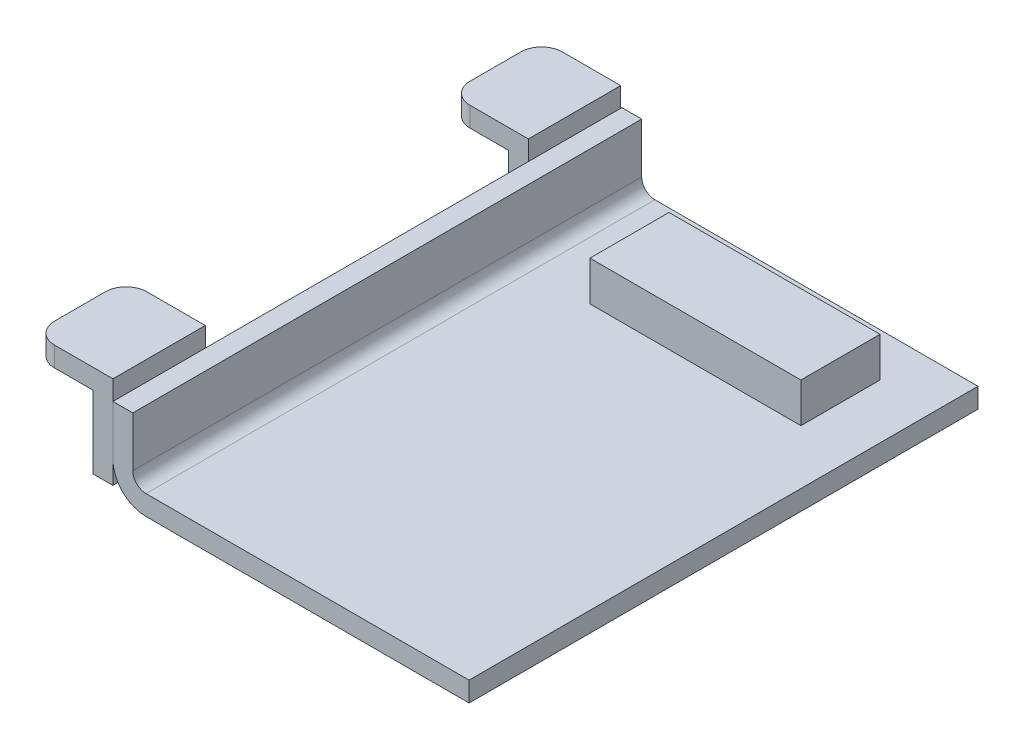
SolidWorks part; units mm, degrees
material "Aluminum Black Anodize"
ref_plane "Front" through (0, 0, 0) normal (0, 0, 1) x (1, 0, 0)
ref_plane "Top" through (0, 0, 0) normal (0, 1, 0) x (1, 0, 0)
ref_plane "Right" through (0, 0, 0) normal (1, 0, 0) x (0, 0, -1)
sketch "Sketch1" plane through (0, 0, 0) normal (0, 0, 1) x (1, 0, 0)
  line L0 (0, 0) -> (0, 20)
  line L1 (0, 20) -> (4.7752, 20)
  line L2 (4.7752, 20) -> (4.7752, 4.7752)
  line L3 (4.7752, 4.7752) -> (85.725, 4.7752)
  line L4 (85.725, 4.7752) -> (85.725, 0)
  line L5 (85.725, 0) -> (0, 0)
  dimension "D1" = 85.725
  dimension "D2" = 20
  dimension "D3" = 4.7752
extrude "Extrude1" add sketch "Sketch1" along normal blind 61.25 and the other way blind 61.25
fillet "Fillet1" radius 3.175 1 edges at (4.7752, 4.7752, 0)
fillet "Fillet2" radius 7.9375 1 edges at (0, 0, 0)
ref_plane "Plane2" through (0, 0, -60.975) normal (0, 0, -1) x (-1, 0, 0)
ref_plane "Plane1" through (47.2248, 0, 0) normal (1, 0, 0) x (0, 0, -1)
sketch "Sketch34" plane through (0, 0, -60.975) normal (0, 0, -1) x (-1, 0, 0)
  line L0 (0, 2.4999) -> (0, 24.7249)
  line L1 (0, 20) -> (0, 7.9375) construction
  line L2 (0, 24.7249) -> (19.05, 24.7249)
  line L3 (19.05, 24.7249) -> (19.05, 19.9497)
  line L4 (19.05, 19.9497) -> (4.7752, 19.9497)
  line L5 (4.7752, 19.9497) -> (4.7752, 2.4999)
  line L6 (4.7752, 2.4999) -> (0, 2.4999)
  line L7 (-4.7752, 20) -> (0, 20) construction
  dimension "D1" = 19.05
  dimension "D2" = 4.7249
  dimension "D3" = 22.225
  dimension "D4" = 4.7752
extrude "Extrude2" add sketch "Sketch34" against normal blind 22.225 separate body
fillet "Fillet3" radius 5 2 edges at (-19.05, 22.3373, -38.75) (-19.05, 22.3373, -60.975)
ref_plane "Plane3" through (0, 0, 61.25) normal (0, 0, 1) x (1, 0, 0)
sketch "Sketch36" plane through (0, 0, 61.25) normal (0, 0, 1) x (1, 0, 0)
  line L0 (0, 2.4999) -> (0, 24.7249) construction
  line L1 (-4.7752, 2.4999) -> (0, 2.4999) construction
  line L2 (-4.7752, 19.9497) -> (-4.7752, 2.4999) construction
  line L3 (-19.05, 19.9497) -> (-4.7752, 19.9497) construction
  line L4 (-19.05, 24.7249) -> (-19.05, 19.9497) construction
  line L5 (0, 24.7249) -> (-19.05, 24.7249) construction
  line L6 (0, 2.4999) -> (0, 24.7249)
  line L7 (-4.7752, 2.4999) -> (0, 2.4999)
  line L8 (-4.7752, 19.9497) -> (-4.7752, 2.4999)
  line L9 (-19.05, 19.9497) -> (-4.7752, 19.9497)
  line L10 (-19.05, 24.7249) -> (-19.05, 19.9497)
  line L11 (0, 24.7249) -> (-19.05, 24.7249)
extrude "Extrude4" [suppressed] add sketch "Sketch36" against normal blind 22.225 separate body
fillet "Fillet4" [suppressed] radius 5
pattern_linear "LPattern1" [suppressed] count 2 spacing 150 of bodies 156
pattern_linear "LPattern2" [suppressed] count 2 spacing 150 of bodies 160 156
sketch "Sketch35" plane through (0, 4.7752, 0) normal (0, 1, 0) x (1, 0, 0)
  line L0 (47.2248, 50.775) -> (47.2248, 41.25) construction
  line L1 (21.8248, 50.775) -> (72.6248, 50.775)
  line L2 (21.8248, 50.775) -> (21.8248, 31.725)
  line L3 (21.8248, 31.725) -> (72.6248, 31.725)
  line L4 (72.6248, 50.775) -> (72.6248, 31.725)
  line L5 (47.2248, 41.25) -> (72.6248, 41.25) construction
  line L6 (47.2248, -13.5987) -> (47.2248, 13.5987) construction
  line L7 (85.725, 61.25) -> (7.9502, 61.25) construction
  dimension "D1" = 20
  dimension "D2" = 19.05
  dimension "D3" = 50.8
extrude "Extrude3" add sketch "Sketch35" along normal blind 9.525 separate body
pattern_linear "LPattern3" [suppressed] count 2 spacing 54 of bodies 159
pattern_linear "LPattern5" [suppressed] count 2 spacing 200 of bodies 160
pattern_linear "LPattern6" [suppressed] count 2 spacing 200 of bodies 156
pattern_linear "LPattern7" count 2 spacing 100 along (0, 0, 1) of bodies 156
pattern_linear "LPattern8" [suppressed] count 2 spacing 100 of bodies 160
